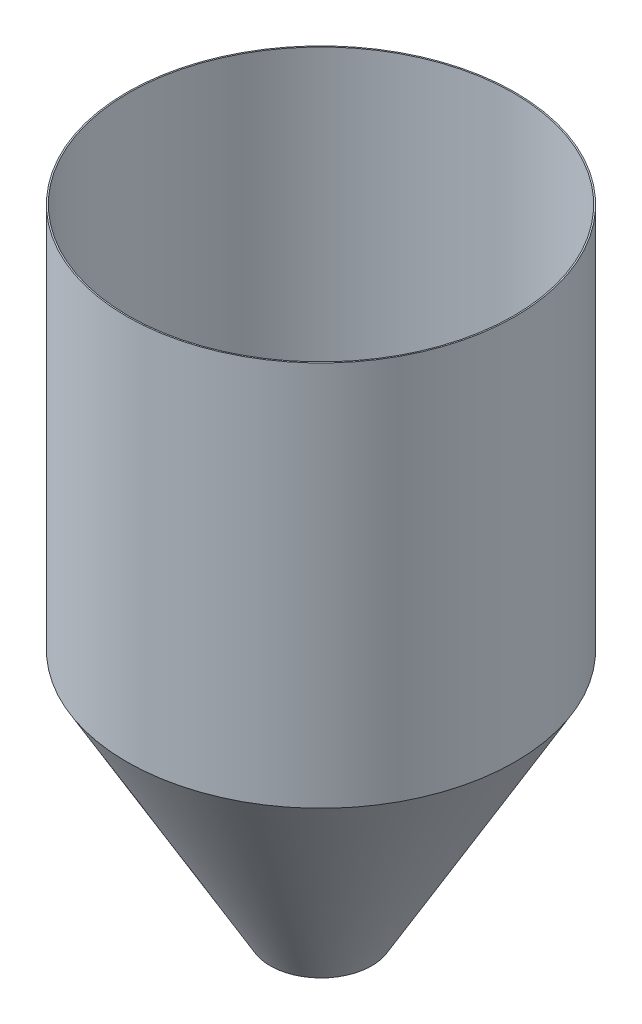
SolidWorks part; units mm, degrees
material "AISI 304"
ref_plane "Front Plane" through (0, 0, 0) normal (0, 0, 1) x (1, 0, 0)
ref_plane "Top Plane" through (0, 0, 0) normal (0, 1, 0) x (1, 0, 0)
ref_plane "Right Plane" through (0, 0, 0) normal (1, 0, 0) x (0, 0, -1)
sketch "Sketch7" plane through (0, 0, 0) normal (0, 1, 0) x (1, 0, 0)
  circle A0 centre (0, 0) radius 228.6
  circle A1 centre (0, 0) radius 230.1875
  dimension "D1" = 457.2
  dimension "D2" = 1.5875
extrude "Boss-Extrude1" add sketch "Sketch7" along normal blind 457.2
sketch "Sketch8" plane through (0, 0, 0) normal (0, 0, 1) x (1, 0, 0)
  line L0 (0, 0) -> (0, -395.9468) construction
  line L1 (0, -395.9468) -> (228.6, 0) construction
  line L2 (-228.6, 0) -> (228.6, 0) construction
  line L3 (-230.1875, 0) -> (230.1875, 0) construction
  line L4 (228.6, 0) -> (230.1875, 0)
  line L5 (228.6, 0) -> (58.6588, -294.3468)
  line L6 (58.6588, -294.3468) -> (60.2463, -294.3468)
  line L7 (60.2463, -294.3468) -> (230.1875, 0)
  dimension "D1" = 457.2
  dimension "D2" = 457.2
  dimension "D3" = 101.6
revolve "Revolve1" add sketch "Sketch8" angle 360 about L0
equation "\"D1@Sketch8\"=\"D2@Sketch8\""
